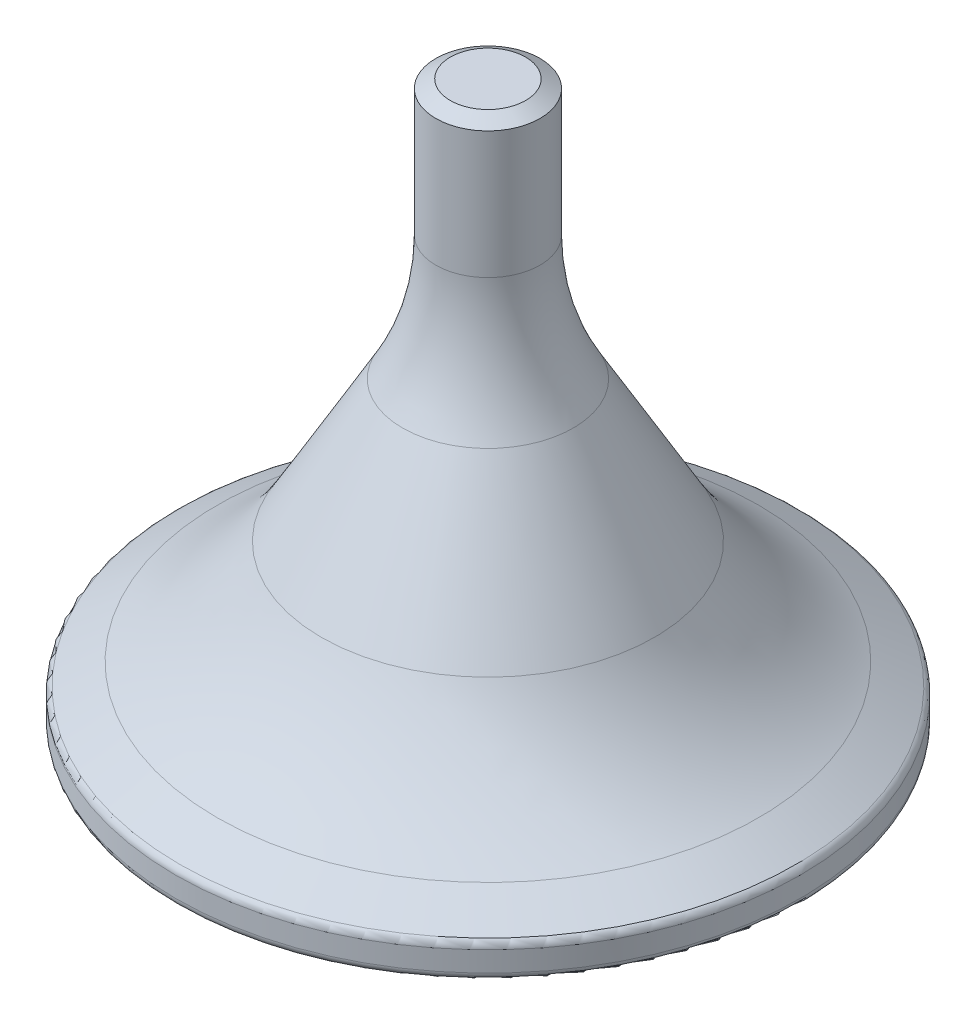
SolidWorks part; units mm, degrees
material "6061-T6 (SS)"
ref_plane "Front Plane" through (0, 0, 0) normal (0, 0, 1) x (1, 0, 0)
ref_plane "Top Plane" through (0, 0, 0) normal (0, 1, 0) x (1, 0, 0)
ref_plane "Right Plane" through (0, 0, 0) normal (1, 0, 0) x (0, 0, -1)
sketch "Sketch3" plane through (0, 0, 0) normal (1, 0, 0) x (0, 0, -1)
  line L0 (0, 0) -> (0, -43.2471) construction
  line L1 (0, 0) -> (3.175, 0)
  line L2 (3.175, 0) -> (3.175, -8.255)
  line L4 (19.05, -32.2338) -> (19.05, -34.2658)
  line L5 (19.05, -34.2658) -> (0, -34.2658)
  line L6 (0, -34.2658) -> (0, 0)
  line L7 (5.207, -15.8385) -> (10.16, -24.4174)
  line L8 (16.51, -30.7674) -> (19.05, -32.2338)
  arc A0 (3.175, -8.255) -> (5.207, -15.8385) centre (18.3421, -8.255) ccw
  arc A1 (10.16, -24.4174) -> (16.51, -30.7674) centre (25.1843, -15.7431) ccw
  point P13 (12.1601, -20.774)
  point P14 (5.2183, -16.4873)
  point P15 (12.9344, -22.9589)
  point P16 (15.502, -23.7755)
  point P17 (9.6155, -20.773)
  point P18 (18.0157, -24.4263)
  point P19 (9.1138, -19.7017)
  point P20 (12.8585, -21.9126)
  point P21 (0, 0)
  point P22 (15.875, -24.8843)
  point P23 (9.399, -21.6632)
  point P24 (10.5655, -22.8297)
  point P25 (0, -43.2471)
  dimension "D2" = 30
  dimension "D6" = 30
  dimension "D1" = 6.35
  dimension "D3" = 8.255
  dimension "D4" = 2.032
  dimension "D5" = 38.1
  dimension "D7" = 2.54
  dimension "D8" = 2.032
  dimension "D9" = 6.35
  dimension "D10" = 34.2658
revolve "Revolve1" add sketch "Sketch3" angle 360 about L0
fillet "Fillet1" radius 0.508 2 edges at (0, -32.2338, 19.05) (0, -34.2658, 19.05)
chamfer "Chamfer1" distance 0.508 angle 60 1 edges at (0, 0, 3.175) first distance on face at (0, 0, 3.175)
sketch "Sketch4" plane through (0, -34.2658, 0) normal (0, -1, 0) x (1, 0, 0)
  line L1 (-9.525, 1.5875) -> (9.525, 1.5875)
  line L2 (-9.525, 1.5875) -> (-9.525, -1.5875)
  line L3 (-9.525, -1.5875) -> (9.525, -1.5875)
  line L4 (9.525, 1.5875) -> (9.525, -1.5875)
  point P4 (-9.525, 0)
  point P5 (0, -1.5875)
  dimension "D1" = 3.175
  dimension "D2" = 19.05
extrude "Cut-Extrude1" cut sketch "Sketch4" against normal blind 4.7625
fillet "Fillet2" radius 1.5875 4 edges at (-9.525, -31.8846, -1.5875) (9.525, -31.8846, -1.5875) (9.525, -31.8846, 1.5875) (-9.525, -31.8846, 1.5875)
